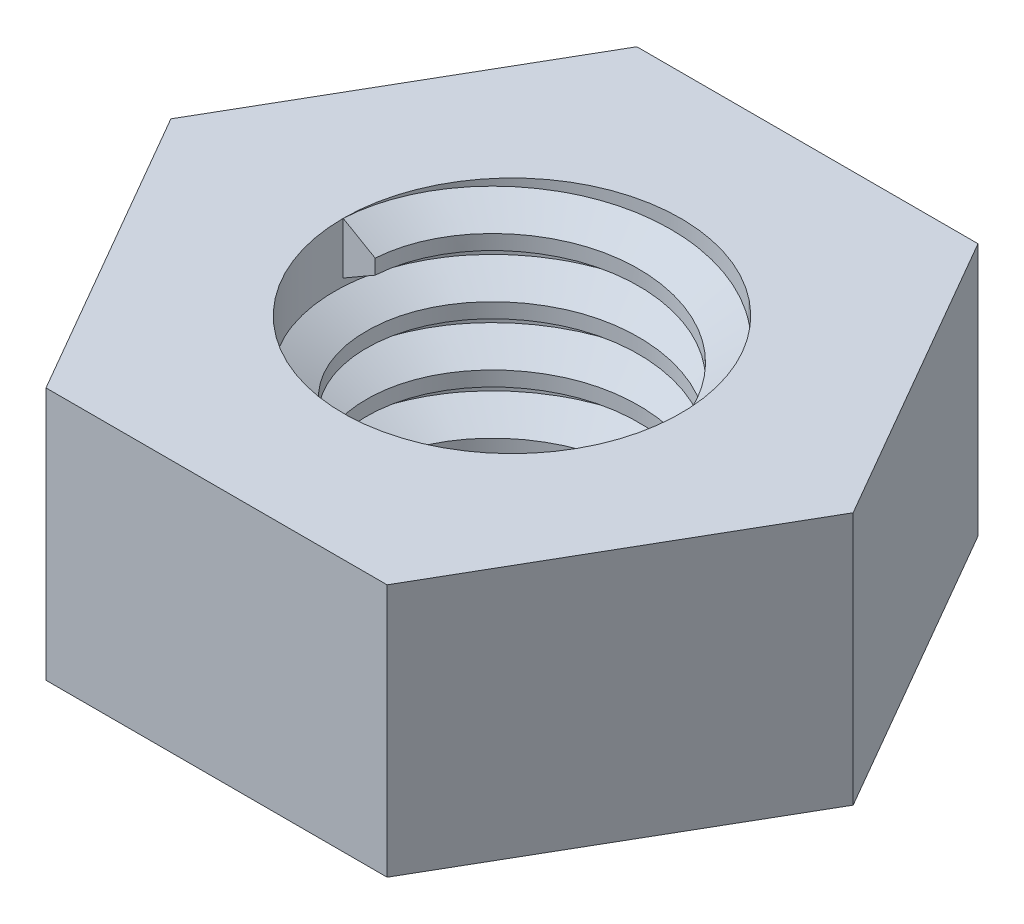
SolidWorks part; units mm, degrees
ref_plane "前基準面" through (0, 0, 0) normal (0, 0, 1) x (1, 0, 0)
ref_plane "上基準面" through (0, 0, 0) normal (0, 1, 0) x (1, 0, 0)
ref_plane "右基準面" through (0, 0, 0) normal (1, 0, 0) x (0, 0, -1)
sketch "草圖1" plane through (0, 0, 0) normal (0, 1, 0) x (1, 0, 0)
  line L1 (4.0415, 0) -> (2.0207, 3.5)
  line L2 (2.0207, 3.5) -> (-2.0207, 3.5)
  line L3 (-2.0207, 3.5) -> (-4.0415, 0)
  line L4 (-4.0415, 0) -> (-2.0207, -3.5)
  line L5 (-2.0207, -3.5) -> (2.0207, -3.5)
  line L6 (2.0207, -3.5) -> (4.0415, 0)
  circle A0 centre (0, 0) radius 3.5 construction
  circle A1 centre (0, 0) radius 2
  dimension "D2" = 4
  dimension "D1" = 7
extrude "填料-伸長1" add sketch "草圖1" along normal blind 3
thread "螺紋1" pitch 0.7 start angle 0, offset 0, length 0, pitch 0.7, diameter 4
ref_plane "平面1" through (-2, 3, 0) normal (0, 0, 1) x (-1, 0, 0)
sketch "螺紋輪廓1" plane through (-2, 3, 0) normal (0, 0, 1) x (-1, 0, 0)
  line L0 (0, 0) -> (0, 0.7) construction
  line L11 (0, 0) -> (0, 0.6125)
  line L12 (0, 0.6125) -> (-0.3789, 0.3937)
  line L13 (-0.3789, 0.3937) -> (-0.3789, 0.2187)
  line L15 (-0.3789, 0.2187) -> (0, 0)
  line L17 (-0.3789, 0.3062) -> (0, 0.3062) construction
  point P2 (0, 0)
  dimension "Pitch" = 0.7
  dimension "Profile_Angle" = 60
  dimension "Profile_Land" = 0.175
  dimension "Profile_Height" = 0.3789
